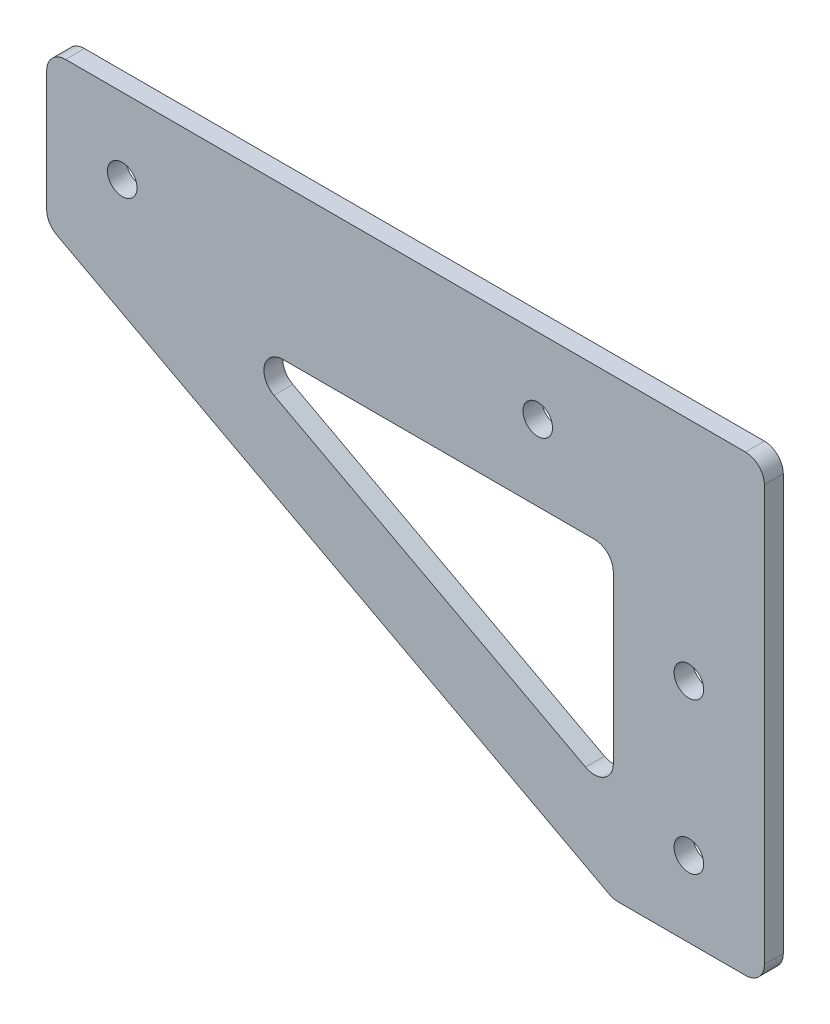
SolidWorks part; units mm, degrees
material "6061-T6 (SS)"
ref_plane "Front Plane" through (0, 0, 0) normal (0, 0, 1) x (1, 0, 0)
ref_plane "Top Plane" through (0, 0, 0) normal (0, 1, 0) x (1, 0, 0)
ref_plane "Right Plane" through (0, 0, 0) normal (1, 0, 0) x (0, 0, -1)
sketch "Sketch1" plane through (0, 0, 0) normal (0, 0, 1) x (1, 0, 0)
  line L0 (-120.65, 50.8) -> (-25.4, 0)
  line L1 (-25.4, 0) -> (0, 0)
  line L2 (-120.65, 50.8) -> (-120.65, 76.2)
  line L3 (-120.65, 76.2) -> (0, 76.2)
  line L4 (0, 0) -> (0, 76.2)
  line L5 (-93.6625, 50.8) -> (-25.4, 50.8)
  line L6 (-25.4, 50.8) -> (-25.4, 14.3933)
  line L7 (-25.4, 14.3933) -> (-93.6625, 50.8)
  point P4 (41.1898, 47.8054)
  point P8 (0, 0)
  dimension "D1" = 120.65
  dimension "D2" = 76.2
  dimension "D3" = 25.4
  dimension "D4" = 25.4
  dimension "D5" = 12.7
extrude "Boss-Extrude1" add sketch "Sketch1" against normal blind 3.175
fillet "Fillet2" radius 3.175 8 edges at (0, 0, -1.5875) (0, 76.2, -1.5875) (-120.65, 76.2, -1.5875) (-25.4, 0, -1.5875) (-120.65, 50.8, -1.5875) (-93.6625, 50.8, -1.5875) (-25.4, 14.3933, -1.5875) (-25.4, 50.8, -1.5875)
sketch "Sketch2" plane through (0, 0, 0) normal (0, 0, 1) x (1, 0, 0)
  line L4 (-120.65, 73.025) -> (-120.65, 52.705) construction
  line L5 (-24.6062, 0) -> (-3.175, 0) construction
  line L6 (0, 3.175) -> (0, 73.025) construction
  line L7 (-3.175, 76.2) -> (-117.475, 76.2) construction
  circle A4 centre (-12.7, 38.1) radius 2.4892
  circle A5 centre (-12.7, 12.7) radius 2.4892
  circle A6 centre (-38.1, 63.5) radius 2.4892
  circle A7 centre (-107.95, 63.5) radius 2.4892
  dimension "D2" = 12.7
  dimension "D9" = 4.9784
  dimension "D1" = 12.7
  dimension "D3" = 25.4
  dimension "D4" = 38.1
  dimension "D5" = 12.7
  dimension "D6" = 12.7
  dimension "D7" = 12.7
  dimension "D8" = 12.7
extrude "Cut-Extrude1" cut sketch "Sketch2" against normal through all contours A7 | A6 | A4 | A5 region at (-12.7, 38.1, 0) region at (-12.7, 12.7, 0) region at (-38.1, 63.5, 0) region at (-107.95, 63.5, 0)
